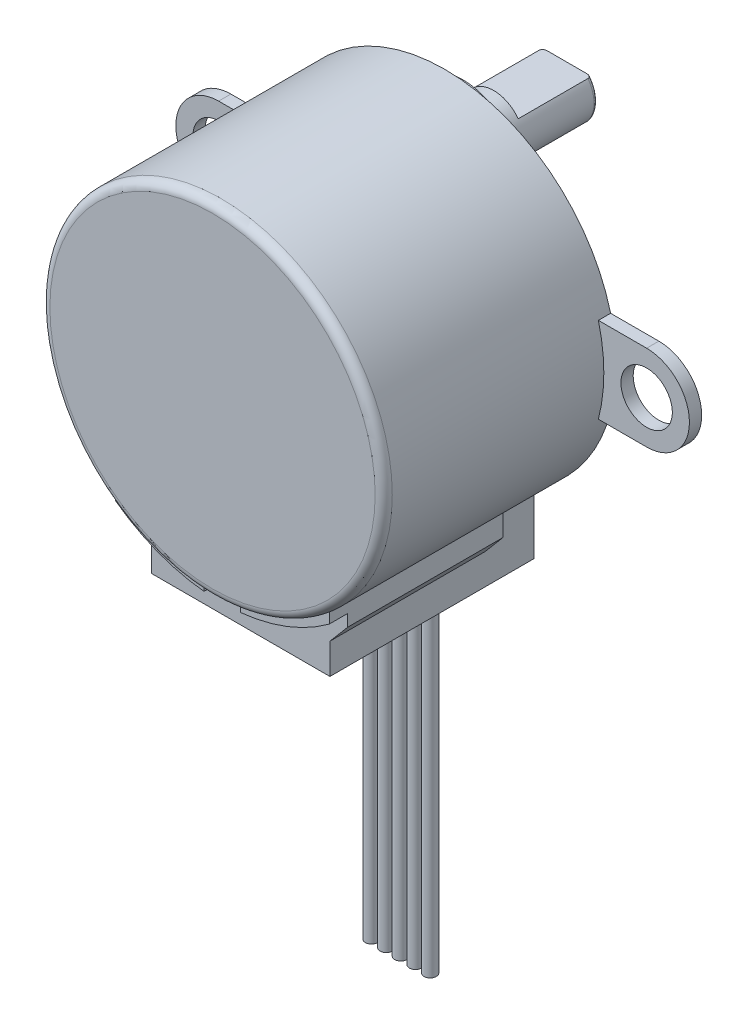
SolidWorks part; units mm, degrees
ref_plane "Front Plane" through (0, 0, 0) normal (0, 0, 1) x (1, 0, 0)
ref_plane "Top Plane" through (0, 0, 0) normal (0, 1, 0) x (1, 0, 0)
ref_plane "Right Plane" through (0, 0, 0) normal (1, 0, 0) x (0, 0, -1)
sketch "Sketch1" plane through (0, 0, 0) normal (0, 0, 1) x (1, 0, 0)
  circle A0 centre (0, 0) radius 14
extrude "Boss-Extrude1" add sketch "Sketch1" along normal blind 19
sketch "Sketch2" plane through (0, 0, 0) normal (0, 0, -1) x (-1, 0, 0)
  circle A0 centre (0, 8) radius 4.5
  point P0 (0, 8)
extrude "Boss-Extrude2" add sketch "Sketch2" along normal blind 1.5
sketch "Sketch3" plane through (0, 0, -1.5) normal (0, 0, -1) x (-1, 0, 0)
  circle A0 centre (0, 8) radius 2.5
extrude "Boss-Extrude3" add sketch "Sketch3" along normal blind 2.5
sketch "Sketch5" plane through (0, 0, -4) normal (0, 0, -1) x (-1, 0, 0)
  line L1 (-2, 9.5) -> (2, 9.5)
  line L3 (-2, 6.5) -> (2, 6.5)
  arc A0 (2, 6.5) -> (2, 9.5) centre (0, 8) ccw
  arc A1 (-2, 9.5) -> (-2, 6.5) centre (0, 8) ccw
extrude "Boss-Extrude5" add sketch "Sketch5" along normal blind 6
fillet "Fillet1" radius 0.3 2 edges at (-2.5, 8, -10) (2.5, 8, -10)
fillet "Fillet2" radius 0.7 1 edges at (14, 0, 19)
sketch "Sketch6" plane through (0, 0, 0) normal (0, 0, -1) x (-1, 0, 0)
  line L0 (0, 3.5) -> (0, -3.5268) construction
  line L1 (-17.5, 3.5) -> (-13.5554, 3.5)
  line L3 (17.5, -3.5) -> (13.5554, -3.5)
  line L4 (-13.5554, -3.5) -> (-17.5, -3.5)
  line L5 (13.5554, 3.5) -> (17.5, 3.5)
  arc A0 (-17.5, 3.5) -> (-17.5, -3.5) centre (-17.5, 0) ccw
  circle A1 centre (-17.5, 0) radius 2.1
  circle A2 centre (0, 8) radius 4.5 construction
  circle A3 centre (0, 8) radius 4.5 construction
  arc A4 (17.5, 3.5) -> (17.5, -3.5) centre (17.5, 0) cw
  circle A5 centre (17.5, 0) radius 2.1
  arc A6 (13.5554, -3.5) -> (13.5554, 3.5) centre (0, 0) ccw
  arc A7 (-13.5554, 3.5) -> (-13.5554, -3.5) centre (0, 0) ccw
  dimension "D1" = 7
  dimension "D2" = 17.5
extrude "Boss-Extrude6" add sketch "Sketch6" against normal blind 1
sketch "Sketch7" plane through (0, 0, 0) normal (0, 0, -1) x (-1, 0, 0)
  line L2 (-7.3, -11.9461) -> (-7.3, -17)
  line L3 (-7.3, -17) -> (7.3, -17)
  line L4 (7.3, -11.9461) -> (7.3, -17)
  arc A0 (-7.3, -11.9461) -> (7.3, -11.9461) centre (0, 0) ccw
  dimension "D1" = 17
  dimension "D2" = 14.6
extrude "Boss-Extrude7" add sketch "Sketch7" against normal blind 16.7
sketch "Sketch8" plane through (0, 0, 16.7) normal (0, 0, 1) x (1, 0, 0)
  line L0 (-7.3, -14.5) -> (-8.75, -12.785)
  line L1 (-7.3, -14.5) -> (-7.3, -11.9461)
  line L2 (-8.75, -10.9287) -> (-8.75, -12.785)
  line L4 (8.75, -10.9287) -> (8.75, -12.785)
  line L9 (8.75, -12.785) -> (7.3, -14.5)
  line L10 (7.3, -11.9461) -> (7.3, -14.5)
  arc A0 (-8.75, -10.9287) -> (-7.3, -11.9461) centre (0, 0) ccw
  arc A1 (7.3, -11.9461) -> (8.75, -10.9287) centre (0, 0) ccw
  dimension "D1" = 17.5
extrude "Boss-Extrude8" add sketch "Sketch8" against normal blind 12.7
sketch "Sketch9" plane through (0, 0, -10) normal (0, 0, -1) x (-1, 0, 0)
  circle A0 centre (0, 8) radius 0.4315
extrude "Cut-Extrude1" cut sketch "Sketch9" against normal blind 0.3
sketch "Sketch10" plane through (0, 0, 16.7) normal (0, 0, 1) x (1, 0, 0)
  line L0 (-8.75, -11.8122) -> (-8.75, -10.9287)
  line L2 (-1.5, -13.9194) -> (-1.5, -14.6233)
  line L4 (1.5, -13.9194) -> (1.5, -14.6233)
  line L7 (8.75, -10.9287) -> (8.75, -11.8122)
  arc A0 (-8.75, -11.8122) -> (-1.5, -14.6233) centre (0, 0) ccw
  arc A1 (-8.75, -10.9287) -> (-1.5, -13.9194) centre (0, 0) ccw
  arc A2 (1.5, -14.6233) -> (8.75, -11.8122) centre (0, 0) ccw
  arc A3 (1.5, -13.9194) -> (8.75, -10.9287) centre (0, 0) ccw
  dimension "D1" = 3
extrude "Boss-Extrude10" add sketch "Sketch10" along normal blind 1.5
sketch "Sketch11" plane through (0, -17, 0) normal (0, -1, 0) x (1, 0, 0)
  line L0 (7.3, 0) -> (-7.3, 0) construction
  line L1 (-3.75, 4.2) -> (3.75, 4.2)
  line L2 (-3.75, 4.2) -> (-3.75, 3)
  line L3 (-3.75, 3) -> (3.75, 3)
  line L4 (3.75, 4.2) -> (3.75, 3)
  dimension "D1" = 7.5
  dimension "D2" = 1.2
  dimension "D3" = 3.75
  dimension "D4" = 3
extrude "Cut-Extrude2" cut sketch "Sketch11" against normal blind 2
sketch "Sketch12" plane through (0, -15, 0) normal (0, -1, 0) x (1, 0, 0)
  line L0 (-3.75, 3.6) -> (3.75, 3.6) construction
  line L1 (-3.75, 4.2) -> (-3.75, 3) construction
  line L2 (3.75, 3) -> (3.75, 4.2) construction
  line L3 (0, 3.6) -> (0, 1.54) construction
  circle A0 centre (-2.4, 3.6) radius 0.5
  circle A1 centre (-1.2, 3.6) radius 0.5
  circle A2 centre (0, 3.6) radius 0.5
  circle A3 centre (1.2, 3.6) radius 0.5
  circle A4 centre (2.4, 3.6) radius 0.5
  dimension "D1" = 1.2
  dimension "D2" = 1.2
extrude "Boss-Extrude11" add sketch "Sketch12" along normal blind 32
